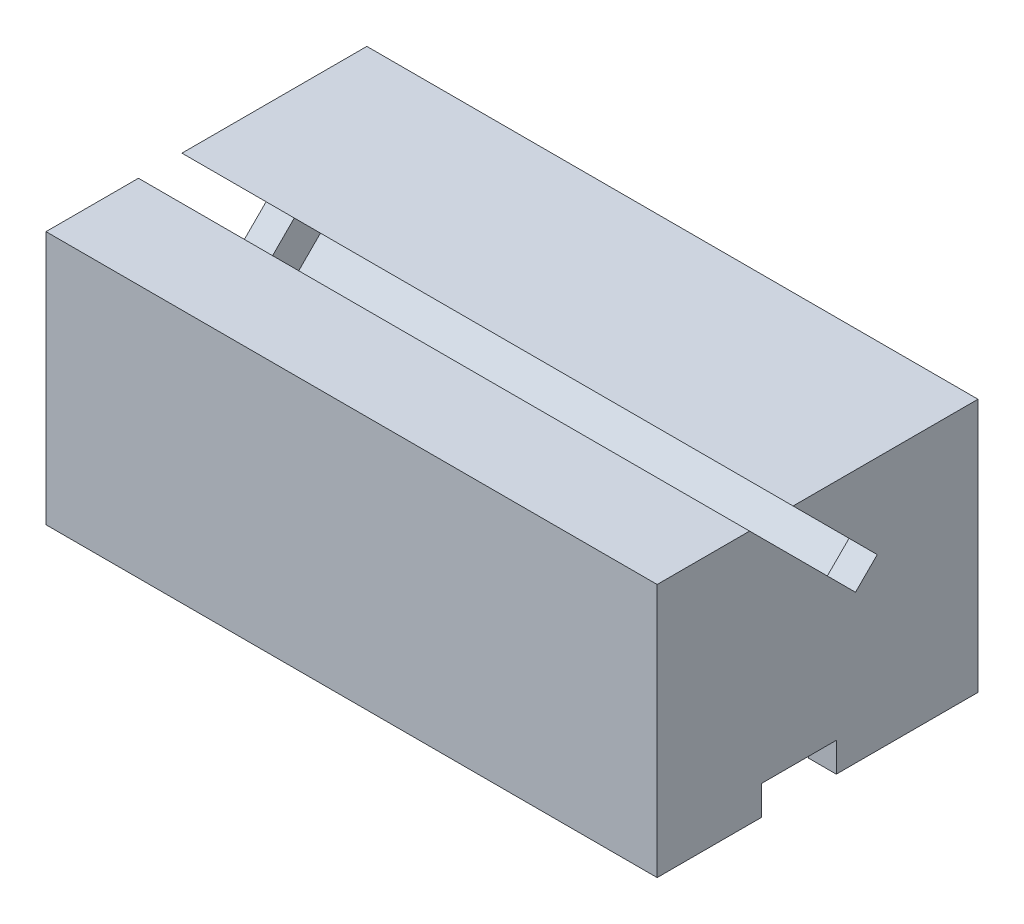
SolidWorks part; units mm, degrees
ref_plane "Front Plane" through (0, 0, 0) normal (0, 0, 1) x (1, 0, 0)
ref_plane "Top Plane" through (0, 0, 0) normal (0, 1, 0) x (1, 0, 0)
ref_plane "Right Plane" through (0, 0, 0) normal (1, 0, 0) x (0, 0, -1)
sketch "Sketch1" plane through (0, 0, 0) normal (1, 0, 0) x (0, 0, -1)
  line L0 (0, 0) -> (0, 24.2836)
  line L1 (0, 24.2836) -> (10, 24.2836)
  line L2 (34.7023, 24.2836) -> (34.7023, 0)
  line L3 (34.7023, 0) -> (0, 0)
  line L4 (10, 24.2836) -> (24.2836, 10)
  line L5 (24.2836, 10) -> (26.6347, 12.3511)
  line L6 (26.6347, 12.3511) -> (14.7023, 24.2836)
  line L7 (23.8063, 15.1796) -> (21.4551, 12.8284)
  line L8 (14.7023, 24.2836) -> (34.7023, 24.2836)
  dimension "D2" = 20.2
  dimension "D3" = 3.325
  dimension "D4" = 10
  dimension "D5" = 20
  dimension "D6" = 10
  dimension "D7" = 4
  dimension "D1" = 45
extrude "Boss-Extrude1" add sketch "Sketch1" along normal blind 66.1 contours L8 L6 L5 L4 L1 L0 L3 L2 region at (0, 11.7022, -17.2327)
extrude "Boss-Extrude2" add sketch "Sketch1<4>" along normal blind 3.05 contours L6 L7 L4 L5 region at (0, 12.5898, -24.0449)
sketch "Sketch1<4>" plane through (0, 0, 0) normal (1, 0, 0) x (0, 0, -1) same geometry as "Sketch1"
ref_plane "Plane1" through (33.05, 0, 0) normal (-1, 0, 0) x (0, 0, 1)
mirror "Mirror1" about plane through (33.05, 0, 0) normal (-1, 0, 0) of "Boss-Extrude2"
sketch "Sketch2" plane through (0, 0, 0) normal (0, 1, 0) x (1, 0, 0)
  line L0 (0, 0) -> (0, 11.2761)
  line L1 (0, 0) -> (0, 10) construction
  line L2 (0, 11.2761) -> (3, 11.2761)
  line L3 (3, 11.2761) -> (3, 7.1761)
  line L4 (3, 7.1761) -> (63.1, 7.1761)
  line L5 (63.1, 7.1761) -> (63.1, 11.2761)
  line L6 (63.1, 11.2761) -> (66.1, 11.2761)
  line L7 (66.1, 0) -> (66.1, 10) construction
  line L8 (66.1, 11.2761) -> (66.1, 0)
  line L9 (66.1, 0) -> (0, 0)
  line L10 (0, 34.7023) -> (0, 19.3761)
  line L11 (0, 14.7023) -> (0, 34.7023) construction
  line L12 (0, 19.3761) -> (3, 19.3761)
  line L13 (3, 19.3761) -> (3, 27.5261)
  line L14 (3, 27.5261) -> (63.1, 27.5261)
  line L15 (63.1, 27.5261) -> (63.1, 19.3761)
  line L16 (63.1, 19.3761) -> (66.1, 19.3761)
  line L17 (66.1, 14.7023) -> (66.1, 34.7023) construction
  line L18 (66.1, 19.3761) -> (66.1, 34.7023)
  line L19 (66.1, 34.7023) -> (0, 34.7023)
  line L20 (33.05, 34.7376) -> (33.05, 0) construction
  line L21 (0, 17.3511) -> (66.1, 17.3511) construction
  line L23 (0, 34.7023) -> (0, 0) construction
  circle A0 centre (12.05, 14.1761) radius 1.5
  circle A1 centre (54.05, 14.1761) radius 1.5
  point P33 (33.05, 34.7023)
  point P38 (0, 17.3511)
  line M21 (0, 0) -> (0, 34.7023)
  line M22 (0, 34.7023) -> (66.1, 34.7023)
  line M23 (66.1, 34.7023) -> (66.1, 0)
  line M24 (66.1, 0) -> (0, 0)
  dimension "D9" = 3
  dimension "D1" = 3
  dimension "D2" = 8.1
  dimension "D3" = 4.1
  dimension "D4" = 8.15
  dimension "D5" = 3
  dimension "D7" = 12.05
  dimension "D8" = 7
extrude "Boss-Extrude3" add sketch "Sketch2" against normal blind 3.175 contours L5 L6 L2 L3 L4 M23 M24 M21 | L16 L15 L14 L13 L12 M21 M22 M23 region at (33.05, 0, -3.866) region at (33.05, 0, -30.398)
extrude "Cut-Extrude1" cut sketch "Sketch2<4>" along normal blind 3 contours A1 | A0 region at (12.05, 0, -14.1761) region at (54.05, 0, -14.1761)
sketch "Sketch2<4>" plane through (0, 0, 0) normal (0, 1, 0) x (1, 0, 0) same geometry as "Sketch2"
chamfer "Chamfer1" distance 1.5 angle 45 4 edges at (12.05, 3, -15.6761) (54.05, 3, -15.6761) (12.05, 0, -15.6761) (54.05, 0, -15.6761)
chamfer "Chamfer3" distance 3.175 angle 45 1 edges at (33.05, 0, -27.5261)
equation "\"D2@Sketch1\"=20.05 + 0.15"
equation "\"D3@Sketch1\"=3.175 + 0.15"
equation "\"D5@Sketch2\"=\"D1@Sketch2\""
equation "\"D2@Sketch2\"=8.00 + 0.10"
equation "\"D1@Sketch2\"=3.05 - 0.05"
equation "\"D4@Sketch2\"=8.05 + 0.10"
equation "\"D3@Sketch2\"=4.00 + 0.10"
